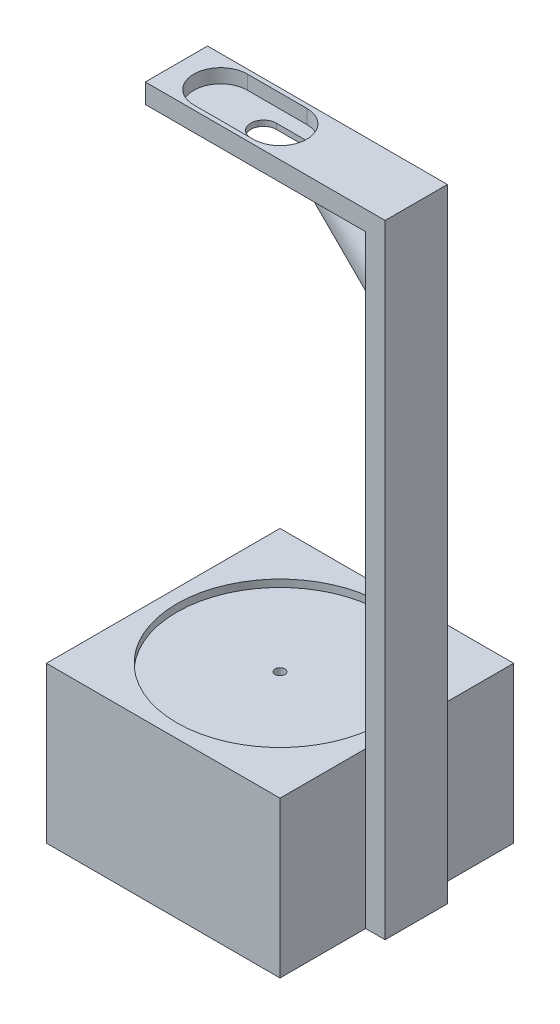
SolidWorks part; units mm, degrees
ref_plane "Front Plane" through (0, 0, 0) normal (0, 0, 1) x (1, 0, 0)
ref_plane "Top Plane" through (0, 0, 0) normal (0, 1, 0) x (1, 0, 0)
ref_plane "Right Plane" through (0, 0, 0) normal (1, 0, 0) x (0, 0, -1)
sketch "Sketch1" plane through (0, 0, 0) normal (0, 1, 0) x (1, 0, 0)
  line L1 (-76.2, -76.2) -> (76.2, -76.2)
  line L2 (-76.2, -76.2) -> (-76.2, 76.2)
  line L3 (-76.2, 76.2) -> (76.2, 76.2)
  line L4 (76.2, -76.2) -> (76.2, 76.2)
  line L5 (-76.2, -76.2) -> (76.2, 76.2) construction
  line L6 (-76.2, 76.2) -> (76.2, -76.2) construction
  point P0 (0, 0)
  dimension "D1" = 152.4
  dimension "D2" = 152.4
extrude "Boss-Extrude1" add sketch "Sketch1" along normal blind 101.6
sketch "Sketch3" plane through (0, 101.6, 0) normal (0, 1, 0) x (1, 0, 0)
  circle A0 centre (0, 0) radius 67.31
  dimension "D1" = 134.62
extrude "Cut-Extrude2" cut sketch "Sketch3" against normal blind 4.7625
ref_plane "Plane1" through (0, 99.3775, 0) normal (0, 1, 0) x (1, 0, 0)
sketch "Sketch4" plane through (0, 99.3775, 0) normal (0, 1, 0) x (1, 0, 0)
  circle A0 centre (0, 0) radius 3.175
  dimension "D1" = 6.35
extrude "Cut-Extrude3" cut sketch "Sketch4" against normal blind 15.6845
sketch "Sketch5" plane through (0, 0, 0) normal (0, -1, 0) x (1, 0, 0)
  circle A0 centre (6.3773, 0) radius 20.32
  dimension "D1" = 40.64
extrude "Cut-Extrude4" cut sketch "Sketch5" against normal blind 92.3925
sketch "Sketch7" plane through (0, 0, -76.2) normal (0, 0, -1) x (-1, 0, 0)
  line L0 (-26.6973, 92.3925) -> (-26.6973, 0) construction
  line L1 (-15.9023, 16.6616) -> (3.1477, 16.6616)
  line L2 (-15.9023, 16.6616) -> (-15.9023, 31.5168)
  line L3 (-15.9023, 31.5168) -> (3.1477, 31.5168)
  line L4 (3.1477, 16.6616) -> (3.1477, 31.5168)
  line L5 (-15.9023, 16.6616) -> (3.1477, 31.5168) construction
  line L6 (-15.9023, 31.5168) -> (3.1477, 16.6616) construction
  point P0 (-6.3773, 24.0892)
  dimension "D1" = 20.32
  dimension "D2" = 19.05
extrude "Cut-Extrude5" cut sketch "Sketch7" against normal blind 60.1345
sketch "Sketch8" plane through (76.2, 0, 0) normal (1, 0, 0) x (0, 0, -1)
  line L0 (-76.2, 101.6) -> (76.2, 101.6) construction
  line L1 (-20.32, 101.6) -> (20.32, 101.6)
  line L2 (-20.32, 101.6) -> (-20.32, 0)
  line L3 (-20.32, 0) -> (20.32, 0)
  line L4 (20.32, 101.6) -> (20.32, 0)
extrude "Boss-Extrude2" add sketch "Sketch8" along normal blind 12.7
sketch "Sketch9" plane through (0, 101.6, 0) normal (0, 1, 0) x (1, 0, 0)
  line L1 (88.9, 20.32) -> (76.2, 20.32)
  line L2 (88.9, 20.32) -> (88.9, -20.32)
  line L3 (88.9, -20.32) -> (76.2, -20.32)
  line L4 (76.2, 20.32) -> (76.2, -20.32)
extrude "Boss-Extrude3" add sketch "Sketch9" along normal blind 304.8
sketch "Sketch10" plane through (76.2, 0, 0) normal (-1, 0, 0) x (0, 0, 1)
  line L0 (20.32, 406.4) -> (20.32, 101.6) construction
  line L1 (-20.32, 406.4) -> (20.32, 406.4)
  line L2 (-20.32, 406.4) -> (-20.32, 393.6801)
  line L3 (-20.32, 393.6801) -> (20.32, 393.6801)
  line L4 (20.32, 406.4) -> (20.32, 393.6801)
extrude "Boss-Extrude4" add sketch "Sketch10" along normal blind 143.764
ref_plane "Plane2" through (-158.74, 158.74, 0) normal (0.7071, -0.7071, 0) x (-0.7071, -0.7071, 0)
sketch "Sketch11" plane through (-158.74, 158.74, 0) normal (0.7071, -0.7071, 0) x (-0.7071, -0.7071, 0)
  circle A2 centre (-301.5618, 0) radius 12.5491
extrude "Boss-Extrude5" add sketch "Sketch11" along normal up to next and the other way up to next
sketch "Sketch14" plane through (0, 406.4, 0) normal (0, 1, 0) x (1, 0, 0)
  line L0 (0, 0) -> (-38.735, 0) construction
  line L1 (0, -17.4625) -> (-38.735, -17.4625)
  line L2 (0, 17.4625) -> (-38.735, 17.4625)
  arc A0 (0, -17.4625) -> (0, 17.4625) centre (0, 0) ccw
  arc A1 (-38.735, 17.4625) -> (-38.735, -17.4625) centre (-38.735, 0) ccw
  point P3 (-19.3675, 0)
  point P8 (-56.1975, 0)
  point P9 (17.4625, 0)
  dimension "D1" = 34.925
  dimension "D2" = 73.66
extrude "Cut-Extrude6" cut sketch "Sketch14" against normal blind 9.144
sketch "Sketch15" plane through (0, 406.4, 0) normal (0, 1, 0) x (1, 0, 0)
  line L0 (-10.7486, 0) -> (8.4758, 0) construction
  line L1 (-10.7486, 8.3183) -> (8.4758, 8.3183)
  line L2 (-10.7486, -8.3183) -> (8.4758, -8.3183)
  arc A0 (-10.7486, 8.3183) -> (-10.7486, -8.3183) centre (-10.7486, 0) ccw
  arc A1 (8.4758, -8.3183) -> (8.4758, 8.3183) centre (8.4758, 0) ccw
  point P3 (-1.1364, 0)
extrude "Cut-Extrude7" cut sketch "Sketch15" against normal blind 48.006
shell "Shell1" thickness 3.81 removed face at (6.3773, 0, -20.32)
